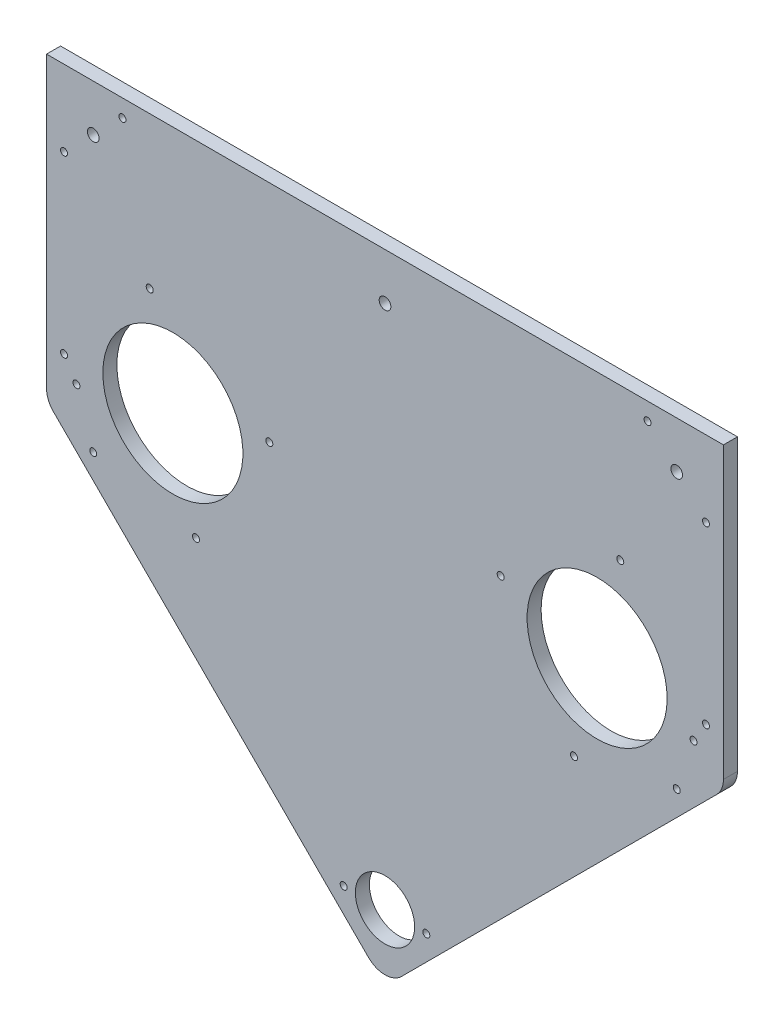
SolidWorks part; units mm, degrees
ref_plane "Front Plane" through (0, 0, 0) normal (0, 0, 1) x (1, 0, 0)
ref_plane "Top Plane" through (0, 0, 0) normal (0, 1, 0) x (1, 0, 0)
ref_plane "Right Plane" through (0, 0, 0) normal (1, 0, 0) x (0, 0, -1)
sketch "Sketch1" plane through (0, 0, 0) normal (0, 0, 1) x (1, 0, 0)
  line L0 (-125, 100) -> (125, 100) construction
  line L1 (-125, 0) -> (125, 0) construction
  line L2 (-137.5158, 87.4842) -> (-125, 100) construction
  line L3 (0, -125) -> (-125, 0) construction
  line L4 (0, -125) -> (-17.7, -125) construction
  line L5 (-125, -17.7) -> (-125, 0) construction
  line L6 (0, -125) -> (0, 100) construction
  line L7 (-145, 120) -> (145, 120)
  line L8 (145, 120) -> (145, -8.2843)
  line L9 (145, -8.2843) -> (0, -153.2843)
  line L10 (0, -153.2843) -> (-145, -8.2843)
  line L11 (-145, -8.2843) -> (-145, 120)
  circle A0 centre (-125, 100) radius 12.7 construction
  circle A1 centre (125, 100) radius 12.7 construction
  circle A4 centre (0, -125) radius 12.7
  circle A5 centre (-137.5158, 87.4842) radius 1.5
  circle A6 centre (-112.4842, 112.5158) radius 1.5
  circle A7 centre (-137.5158, 12.5158) radius 1.5
  circle A8 centre (-125, -17.7) radius 1.5
  circle A9 centre (-17.7, -125) radius 1.5
  circle A10 centre (-125, 0) radius 12.7 construction
  circle A11 centre (125, 0) radius 12.7 construction
  circle A12 centre (-125, 0) radius 17.7 construction
  circle A13 centre (-125, 100) radius 17.7 construction
  circle A15 centre (17.7, -125) radius 1.5
  circle A16 centre (125, -17.7) radius 1.5
  circle A17 centre (137.5158, 12.5158) radius 1.5
  circle A18 centre (137.5158, 87.4842) radius 1.5
  circle A19 centre (112.4842, 112.5158) radius 1.5
  circle A20 centre (0, 100) radius 2.5
  circle A21 centre (-125, 100) radius 2.5
  circle A22 centre (125, 100) radius 2.5
  point P12 (0, 100)
  point P45 (0, 120)
  dimension "D1" = 25.4
  dimension "D5" = 3
  dimension "D2" = 5
  dimension "D4" = 100
  dimension "D7" = 135
  dimension "D8" = 45
  dimension "D9" = 250
  dimension "D10" = 45
  dimension "D11" = 20
  dimension "D12" = 20
  dimension "D13" = 20
  dimension "D14" = 20
  dimension "D15" = 20
  dimension "D6" = 17.7
  dimension "D16" = 17.7
  dimension "D3" = 225
extrude "Boss-Extrude1" add sketch "Sketch1" along normal blind 6
fillet "Fillet1" radius 10 3 edges at (-145, -8.2843, 3) (145, -8.2843, 3) (0, -153.2843, 3)
sketch "Sketch2" plane through (0, 0, 6) normal (0, 0, 1) x (1, 0, 0)
  line L0 (132.2073, 3.8685) -> (49.5554, 23.7093) construction
  line L1 (80.961, -27.5371) -> (100.8017, 55.1149) construction
  line L2 (0, 0) -> (0, 100) construction
  circle A0 centre (90.8813, 13.7889) radius 42.5 construction
  circle A1 centre (49.5554, 23.7093) radius 1.5
  circle A2 centre (100.8017, 55.1149) radius 1.5
  circle A3 centre (132.2073, 3.8685) radius 1.5
  circle A4 centre (80.961, -27.5371) radius 1.5
  circle A5 centre (90.8813, 13.7889) radius 30
  circle A6 centre (-49.5554, 23.7093) radius 1.5
  circle A7 centre (-100.8017, 55.1149) radius 1.5
  circle A8 centre (-80.961, -27.5371) radius 1.5
  circle A9 centre (-132.2073, 3.8685) radius 1.5
  circle A10 centre (-90.8813, 13.7889) radius 42.5 construction
  circle A11 centre (-90.8813, 13.7889) radius 30
  point P6 (90.8813, 13.7889)
  point P27 (-90.8813, 13.7889)
  dimension "D1" = 85
  dimension "D2" = 3
  dimension "D3" = 60
extrude "Cut-Extrude1" cut sketch "Sketch2" against normal blind 10
equation "\"carbon_fiber_tube_diam\"= 1in"
equation "\"clip_tube_diam\"= 5mm"
equation "\"D1@Sketch1\"=\"carbon_fiber_tube_diam\""
equation "\"middle_tube_len\"= 500mm"
equation "\"horizontal_pipe_spacing\"= 250mm"
equation "\"D9@Sketch1\"= \"horizontal_pipe_spacing\""
equation "\"battery_height\"= 3.937in"
equation "\"battery_width\"= 6.693in"
equation "\"carbon_clip_tubes_center_distance\"= 17.7mm"
equation "\"carbon_clip_tubes_center_angle\"= 135"
equation "\"D6@Sketch1\"=\"carbon_clip_tubes_center_distance\""
equation "\"D7@Sketch1\"=\"carbon_clip_tubes_center_angle\""
equation "\"D16@Sketch1\"=\"carbon_clip_tubes_center_distance\""
equation "\"cosmetic_tube_diam\"= 3mm"
equation "\"D5@Sketch1\"=\"cosmetic_tube_diam\""
equation "\"D2@Sketch1\"=\"clip_tube_diam\""
equation "\"vertical_pipe_spacing\"= 225mm"
equation "\"D3@Sketch1\"=\"vertical_pipe_spacing\""
